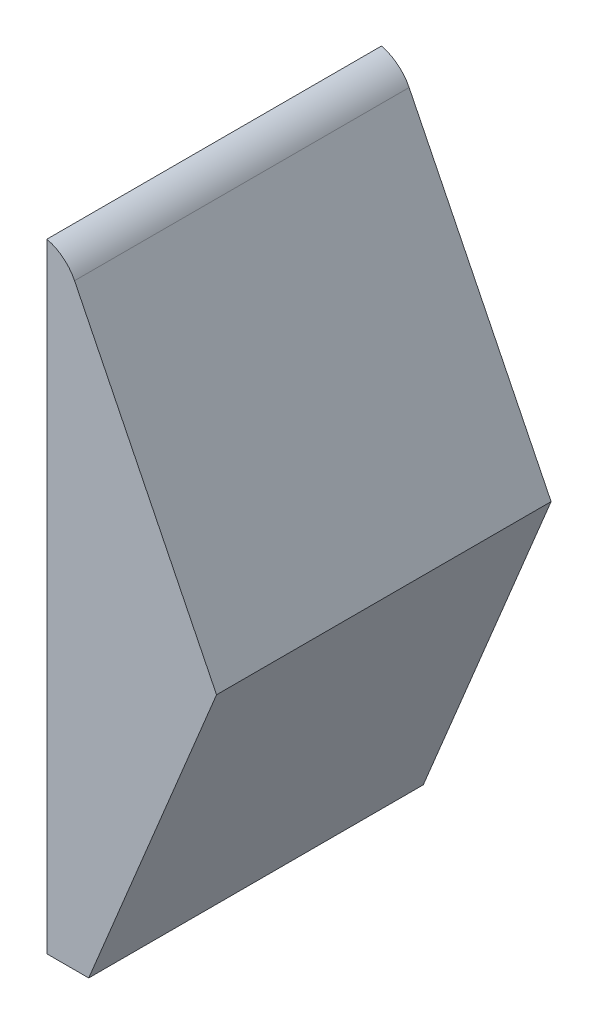
SolidWorks part; units mm, degrees
material "Custom Plastic"
ref_plane "X-Y Datum" through (0, 0, 0) normal (0, 0, 1) x (1, 0, 0)
ref_plane "X-Z Datum" through (0, 0, 0) normal (0, 1, 0) x (1, 0, 0)
ref_plane "Y-Z Datum" through (0, 0, 0) normal (1, 0, 0) x (0, 0, -1)
sketch "Sketch1" plane through (0, 0, 0) normal (0, 0, 1) x (1, 0, 0)
  line L0 (0, 0) -> (0, 74)
  line L1 (0, 0) -> (5, 0)
  line L3 (5, 0) -> (20.2812, 36.966)
  line L4 (0, 74) -> (2, 74)
  line L5 (2, 74) -> (20.2812, 36.966)
  dimension "D1" = 74
  dimension "D2" = 40
  dimension "D3" = 2
  dimension "D4" = 5
extrude "Boss-Extrude1" add sketch "Sketch1" against normal mid plane 40
shell "Shell1" [suppressed] thickness 2
sketch "Sketch2" [suppressed] plane through (2, 0, 0) normal (1, 0, 0) x (0, 0, -1)
  line L4 (-18, 69.4817) -> (-18, 2)
  line L5 (-18, 2) -> (18, 2)
  line L6 (18, 2) -> (18, 69.4817)
  line L7 (18, 69.4817) -> (-18, 69.4817)
  line L8 (-18, 69.4817) -> (-18, 2)
  line L9 (-18, 2) -> (18, 2)
  line L10 (18, 2) -> (18, 69.4817)
  line L12 (18, 69.4817) -> (-18, 69.4817)
  dimension "D1" = 0
extrude "Cut-Extrude1" [suppressed] cut sketch "Sketch2" against normal through all
fillet "Fillet1" [suppressed] radius 20
fillet "Fillet3" radius 5 1 edges at (2, 74, 0)
